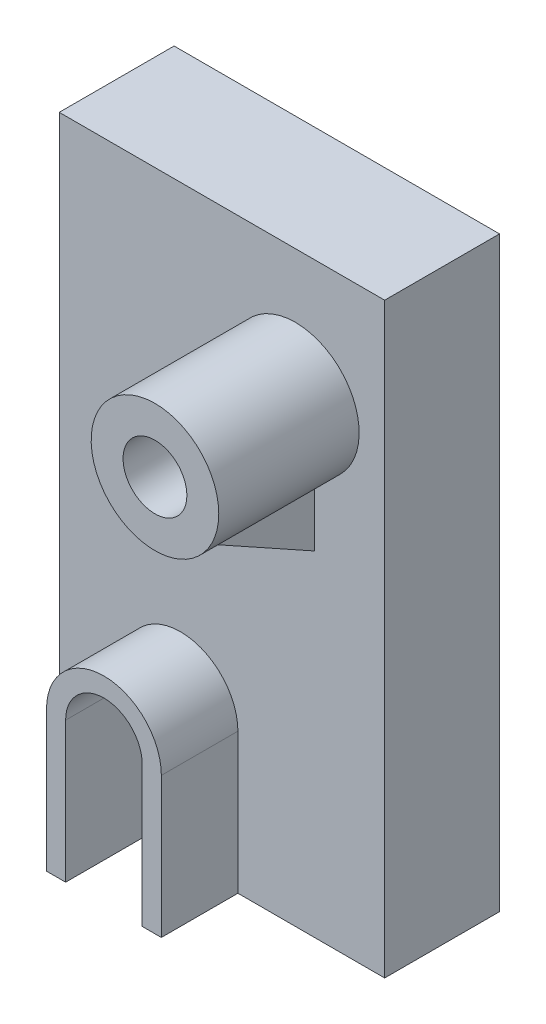
SolidWorks part; units mm, degrees
material "Легированная сталь (SS)"
ref_plane "Спереди" through (0, 0, 0) normal (0, 0, 1) x (1, 0, 0)
ref_plane "Сверху" through (0, 0, 0) normal (0, 1, 0) x (1, 0, 0)
ref_plane "Справа" through (0, 0, 0) normal (1, 0, 0) x (0, 0, -1)
sketch "Эскиз1" plane through (0, 0, 0) normal (0, 0, 1) x (1, 0, 0)
  line L0 (19, 0) -> (19, 50000) construction
  line L1 (0, 0) -> (13, 0)
  line L2 (0, 0) -> (0, 92)
  line L3 (0, 92) -> (51, 92)
  line L4 (51, 0) -> (51, 92)
  line L5 (28, 0) -> (28, 22)
  line L6 (10, 0) -> (10, 22)
  line L7 (25, 0) -> (25, 22)
  line L8 (13, 0) -> (13, 22)
  line L9 (25, 0) -> (51, 0)
  line L10 (37, 77.6263) -> (37, 50077.6263) construction
  line L11 (34, 52.4606) -> (40, 52.4606)
  line L12 (34, 52.4606) -> (34, 62.4606)
  line L13 (40, 52.4606) -> (40, 62.4606)
  arc A0 (25, 22) -> (13, 22) centre (19, 22) ccw
  arc A1 (28, 22) -> (10, 22) centre (19, 22) ccw
  circle A2 centre (37, 72) radius 10
  circle A3 centre (37, 72) radius 5
  dimension "D8" = 50
  dimension "D10" = 20
  dimension "D11" = 10
  dimension "D1" = 92
  dimension "D2" = 51
  dimension "D3" = 32
  dimension "D4" = 22
  dimension "D5" = 28
  dimension "D6" = 22
  dimension "D7" = 25
  dimension "D9" = 14
  dimension "D13" = 6
  dimension "D14" = 10
extrude "Бобышка-Вытянуть2" add sketch "Эскиз1" along normal blind 18 contours A1 L5 L9 L4 L3 L2 L1 L6 A2 L13 L11 L12 region at (25.2681, 48.0024, 0)
extrude "Бобышка-Вытянуть3" add sketch "Эскиз1<6>" along normal blind 30 contours L5 A1 L6 L1 L8 A0 L7 L9 region at (10.3585, 11, 0)
sketch "Эскиз1<6>" plane through (0, 0, 0) normal (0, 0, 1) x (1, 0, 0) same geometry as "Эскиз1"
extrude "Бобышка-Вытянуть4" add sketch "Эскиз1<8>" along normal blind 40 contours A2 A3 region at (31.2513, 79.8342, 0)
sketch "Эскиз1<8>" plane through (0, 0, 0) normal (0, 0, 1) x (1, 0, 0) same geometry as "Эскиз1"
extrude "Бобышка-Вытянуть5" add sketch "Эскиз1<9>" along normal blind 36 contours A2 L12 L11 L13 region at (37, 57.3073, 0)
sketch "Эскиз1<9>" plane through (0, 0, 0) normal (0, 0, 1) x (1, 0, 0) same geometry as "Эскиз1"
sketch "Эскиз3" plane through (40, 0, 0) normal (1, 0, 0) x (0, 0, -1)
  line L0 (-36, 62.4606) -> (-18, 52.4606)
  line L1 (-36, 62.4606) -> (-36, 52.4606)
  line L2 (-36, 52.4606) -> (-18, 52.4606)
extrude "Вырез-Вытянуть1" cut sketch "Эскиз3" against normal through all
